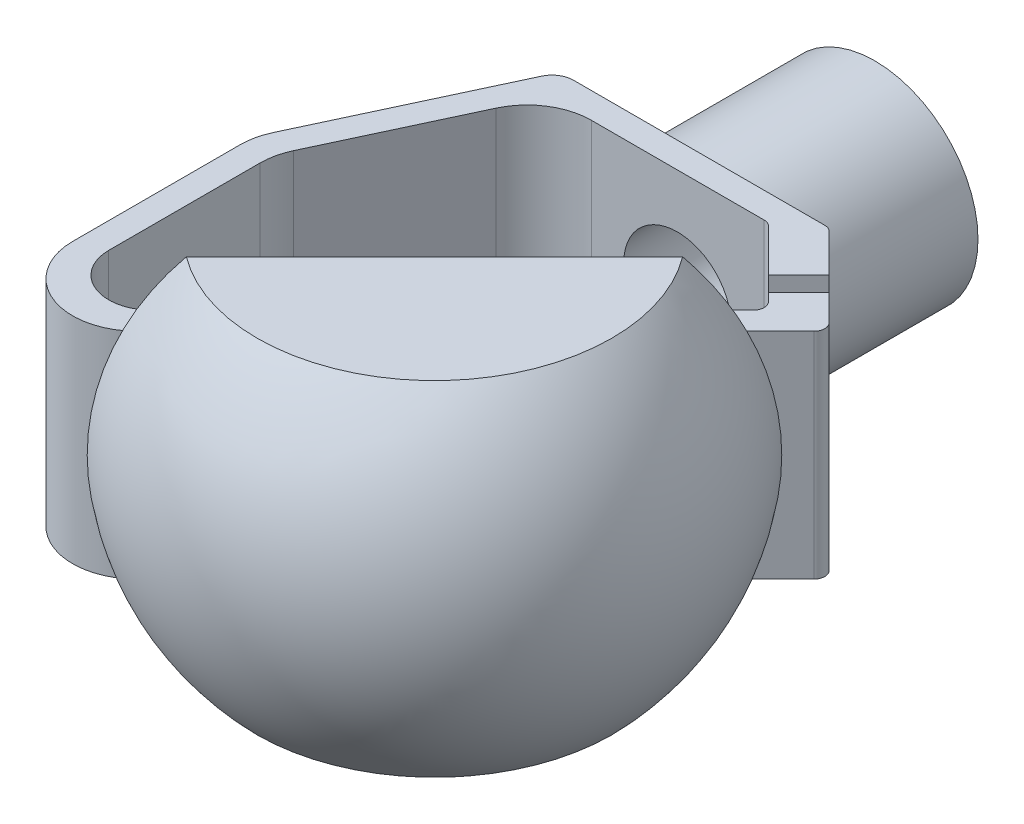
SolidWorks part; units mm, degrees
ref_plane "前视基准面" through (0, 0, 0) normal (0, 0, 1) x (1, 0, 0)
ref_plane "上视基准面" through (0, 0, 0) normal (0, 1, 0) x (1, 0, 0)
ref_plane "右视基准面" through (0, 0, 0) normal (1, 0, 0) x (0, 0, -1)
sketch "Sketch1" plane through (0, 0, 0) normal (0, 0, 1) x (1, 0, 0)
  circle A0 centre (0, 0) radius 3
  circle A1 centre (0, 0) radius 4.5
  dimension "D1" = 6
  dimension "D2" = 9
extrude "Boss-Extrude1" [suppressed] add sketch "Sketch1" along normal blind 5
sketch "Sketch2" [suppressed] plane through (0, 0, 0) normal (1, 0, 0) x (0, 0, -1)
  line L0 (5.3369, 0) -> (-52.9803, 0) construction
  line L1 (-5, 5) -> (-5, -5)
  line L2 (-5, 4.5) -> (-5, -4.5) construction
  line L3 (-6.5, 5) -> (-6.5, -1.5693)
  line L7 (-6.5, 3.4118) -> (-6.5, -3.739) construction
  line L8 (-5, 5) -> (-6.5, 5)
  arc A0 (-8.6581, -6.1507) -> (-8.6581, 6.1507) centre (-12, 0) cw
  arc A2 (-8.6581, -6.1507) -> (-5, -5) centre (-3.8839, -14.9375) cw
  arc A3 (-9.3742, -4.8327) -> (-9.5885, 4.9431) centre (-12, 0) cw
  arc A5 (-9.3742, -4.8327) -> (-8.3381, -4.3351) centre (-3.8839, -14.9375) cw
  arc A6 (-8.6581, 6.1507) -> (-5, 5) centre (-5.9228, 8.4562) ccw construction
  arc A7 (-9.5885, 4.9431) -> (-6.5, 3.4118) centre (-5.9228, 8.4562) ccw construction
  arc A8 (-8.6581, 6.1507) -> (-6.96, 4.8578) centre (-12, 0) cw
  arc A9 (-9.5885, 4.9431) -> (-8.04, 3.8169) centre (-12, 0) cw
  arc A10 (-6.96, 4.8578) -> (-8.04, 3.8169) centre (-7.5, 4.3373) cw
  arc A11 (-9.3742, -4.8327) -> (-6.5, -3.739) centre (-3.8839, -14.9375) cw construction
  arc A12 (-6.5, -1.5693) -> (-8.3381, -4.3351) centre (-9.5, -1.5693) cw
  point P14 (-5, 0)
  dimension "D1" = 7
  dimension "D2" = 7
  dimension "D3" = 10
  dimension "D6" = 3
  dimension "D5" = 10
  dimension "D7" = 2.5
  dimension "D4" = 1.5
extrude "Boss-Extrude2" [suppressed] add sketch "Sketch2" along normal mid plane 5
sketch "Sketch4" [suppressed] plane through (0, 0, 5) normal (0, 0, -1) x (-1, 0, 0)
  line L2 (-2.5, 1.6583) -> (-2.5, -1.6583)
  line L3 (-2.5, 1.6583) -> (-2.5, -1.6583)
  line L4 (2.5, -1.6583) -> (2.5, 1.6583)
  line L5 (2.5, -1.6583) -> (2.5, 1.6583)
  arc A1 (2.5, 1.6583) -> (-2.5, 1.6583) centre (0, 0) ccw
  arc A4 (2.5, 1.6583) -> (-2.5, 1.6583) centre (0, 0) ccw
  arc A5 (-2.5, -1.6583) -> (2.5, -1.6583) centre (0, 0) ccw
  arc A6 (-2.5, -1.6583) -> (2.5, -1.6583) centre (0, 0) ccw
  dimension "D1" = 0
extrude "Cut-Extrude1" [suppressed] cut sketch "Sketch4" against normal blind 10
sketch "Sketch5" [suppressed] plane through (0, 0, 0) normal (0, 1, 0) x (1, 0, 0)
  line L0 (0, 5.4882) -> (0, -28.2063) construction
  line L1 (-3, -6.75) -> (-2.5, -5.2112)
  line L2 (2.5, -6.75) -> (-2.5, -6.75) construction
  line L3 (-2.5, -6.96) -> (-2.5, -19) construction
  line L4 (-2.5, -5.2112) -> (-7.6027, -5.2112)
  line L5 (-7.6027, -5.2112) -> (-7.6027, -6.75)
  line L6 (-7.6027, -6.75) -> (-3, -6.75)
  line L7 (7.6027, -6.75) -> (3, -6.75)
  line L8 (7.6027, -5.2112) -> (7.6027, -6.75)
  line L9 (2.5, -5.2112) -> (7.6027, -5.2112)
  line L10 (3, -6.75) -> (2.5, -5.2112)
  dimension "D1" = 6
  dimension "D2" = 72
extrude "Cut-Extrude2" [suppressed] cut sketch "Sketch5" along normal blind 10
sketch "Sketch6" [suppressed] plane through (0, 0, 5) normal (0, 0, -1) x (-1, 0, 0)
  line L0 (2.5, 5) -> (0, 5) construction
  line L1 (2.5, 4.3301) -> (2.5, 5) construction
  line L2 (-2.5, 5) -> (-2.5, 4.3301) construction
  line L3 (0, 5) -> (-2.5, 5) construction
  line L4 (2.5, 5) -> (0, 5)
  line L5 (2.5, 4.3301) -> (2.5, 5)
  line L6 (-2.5, 5) -> (-2.5, 4.3301)
  line L7 (0, 5) -> (-2.5, 5)
  arc A0 (2.5, 4.3301) -> (0, 5) centre (0, 0) ccw construction
  arc A1 (0, 5) -> (-2.5, 4.3301) centre (0, 0) ccw construction
  arc A2 (2.5, 4.3301) -> (0, 5) centre (0, 0) ccw
  arc A3 (0, 5) -> (-2.5, 4.3301) centre (0, 0) ccw
extrude "Cut-Extrude3" [suppressed] cut sketch "Sketch6" against normal blind 1.5 contours A2 L5 L4
sketch "Sketch7" [suppressed] plane through (0, 0, 0) normal (0, 1, 0) x (1, 0, 0)
  line L0 (0, 0) -> (0, -16.4879) construction
  line L1 (-0.6, -10) -> (-0.6, -15)
  line L2 (-0.6, -15) -> (-2.1, -15)
  line L3 (-2.1, -15) -> (-2.1, -13.5)
  line L4 (-2.1, -10) -> (-0.6, -10)
  line L11 (-5.15, -13) -> (-7.8791, -13)
  line L13 (-5.75, -12.4) -> (-7.1299, -12.4)
  line L15 (-5.75, -12.4) -> (-2.6, -12.4)
  line L17 (-2.1, -11.9) -> (-2.1, -10)
  line L18 (-4.5, -5) -> (-1.5, -5)
  line L20 (-3.5, -7) -> (-1.5, -7)
  line L21 (-1.5, -7) -> (-1.5, -5)
  line L23 (-4.5, -5) -> (4.5, -5) construction
  line L27 (-5.15, -13) -> (-2.6, -13)
  line L36 (5.15, -13) -> (2.6, -13)
  line L40 (1.5, -7) -> (1.5, -5)
  line L41 (3.5, -7) -> (1.5, -7)
  line L42 (4.5, -5) -> (1.5, -5)
  line L43 (2.1, -11.9) -> (2.1, -10)
  line L44 (5.75, -12.4) -> (2.6, -12.4)
  line L45 (5.75, -12.4) -> (7.1299, -12.4)
  line L46 (5.15, -13) -> (7.8791, -13)
  line L47 (2.1, -10) -> (0.6, -10)
  line L48 (2.1, -15) -> (2.1, -13.5)
  line L49 (0.6, -15) -> (2.1, -15)
  line L50 (0.6, -10) -> (0.6, -15)
  arc A0 (-4.5, -5) -> (-7.8791, -13) centre (0, -11.6144) ccw
  arc A2 (-7.3792, -12.1687) -> (-7.2113, -9.9538) centre (0, -11.6144) cw
  arc A10 (-7.1299, -12.4) -> (-7.3792, -12.1687) centre (-7.1299, -12.15) cw
  arc A17 (-2.6, -13) -> (-2.1, -13.5) centre (-2.6, -13.5) cw
  arc A18 (-2.6, -12.4) -> (-2.1, -11.9) centre (-2.6, -11.9) ccw
  arc A19 (-7.2113, -9.9538) -> (-3.5, -7) centre (-3.5, -10.8084) cw
  arc A36 (7.2113, -9.9538) -> (3.5, -7) centre (3.5, -10.8084) ccw
  arc A37 (2.6, -12.4) -> (2.1, -11.9) centre (2.6, -11.9) cw
  arc A38 (2.6, -13) -> (2.1, -13.5) centre (2.6, -13.5) ccw
  arc A39 (7.1299, -12.4) -> (7.3792, -12.1687) centre (7.1299, -12.15) ccw
  arc A40 (7.3792, -12.1687) -> (7.2113, -9.9538) centre (0, -11.6144) ccw
  arc A41 (4.5, -5) -> (7.8791, -13) centre (0, -11.6144) cw
  point P37 (-2.1, -12.4)
  dimension "D4" = 8
  dimension "D1" = 0.6
  dimension "D3" = 5
  dimension "D6" = 2.4
  dimension "D11" = 0.5
  dimension "D12" = 0.25
  dimension "1.2" = 1.2
  dimension "D2" = 1.5
  dimension "D5" = 3
  dimension "D15" = 2
  dimension "D18" = 2
  dimension "D19" = 2
  dimension "0.5" = 0.6
extrude "Boss-Extrude3" [suppressed] add sketch "Sketch7" along normal mid plane 6
sketch "Sketch9" [suppressed] plane through (0, 0, 7) normal (0, 0, 1) x (1, 0, 0)
  circle A0 centre (0, 0) radius 1.5
  circle A2 centre (0, 0) radius 4.5
  arc A3 (3.3541, 3) -> (2.5, 3.7417) centre (0, 0) ccw construction
  dimension "D1" = 3
extrude "Boss-Extrude9" [suppressed] add sketch "Sketch9" against normal blind 2
sketch "Sketch10" [suppressed] plane through (0, 0, 15) normal (0, 0, 1) x (1, 0, 0)
  circle A0 centre (0, 0) radius 0.6
  circle A1 centre (0, 0) radius 2
  dimension "D1" = 1.2
  dimension "D2" = 4
extrude "Boss-Extrude10" [suppressed] add sketch "Sketch10" against normal up to surface (5 mm away)
sketch "Sketch11" [suppressed] plane through (0, 0, 15) normal (0, 0, 1) x (1, 0, 0)
  line L0 (13.3922, 0) -> (-14.7253, 0) construction
  line L1 (0.6, 1.9079) -> (4, 1.9079)
  line L2 (4, 1.9079) -> (6.219, 3.189)
  line L3 (6.219, 3.189) -> (-6.219, 3.189)
  line L4 (0, 3.189) -> (0, 2) construction
  line L5 (-4, 1.9079) -> (-6.219, 3.189)
  line L6 (-0.6, 1.9079) -> (-4, 1.9079)
  line L7 (-0.6, -1.9079) -> (-4, -1.9079)
  line L8 (-4, -1.9079) -> (-6.219, -3.189)
  line L9 (6.219, -3.189) -> (-6.219, -3.189)
  line L10 (4, -1.9079) -> (6.219, -3.189)
  line L11 (0.6, -1.9079) -> (4, -1.9079)
  arc A0 (0.6, 1.9079) -> (-0.6, 1.9079) centre (0, 0) ccw construction
  arc A1 (0.6, 1.9079) -> (-0.6, 1.9079) centre (0, 0) ccw
  arc A2 (0.6, -1.9079) -> (-0.6, -1.9079) centre (0, 0) cw
  line M9 (-0.6, -3) -> (-0.6, -1.9079)
  arc M10 (-0.6, -1.9079) -> (0.6, -1.9079) centre (0, 0) ccw
  line M11 (0.6, -1.9079) -> (0.6, -3)
  line M12 (0.6, -3) -> (2.1, -3)
  line M13 (2.1, -3) -> (2.1, 3)
  line M14 (2.1, 3) -> (0.6, 3)
  line M15 (0.6, 3) -> (0.6, 1.9079)
  arc M16 (0.6, 1.9079) -> (-0.6, 1.9079) centre (0, 0) ccw
  line M17 (-0.6, 1.9079) -> (-0.6, 3)
  line M18 (-0.6, 3) -> (-2.1, 3)
  line M19 (-2.1, 3) -> (-2.1, -3)
  line M20 (-2.1, -3) -> (-0.6, -3)
  dimension "D1" = 30
  dimension "D2" = 4
extrude "Cut-Extrude5" [suppressed] cut sketch "Sketch11" against normal blind 5 contours L6 L1 L2 L3 L5 M19 M18 M17 M16 M15 M14 M13 | L11 L7 L8 L9 L10 M13 M12 M11 M10 M9 M20 M19
sketch "Sketch12" [suppressed] plane through (0, 0, 15) normal (0, 0, 1) x (1, 0, 0)
  line L0 (-0.6, 1.9079) -> (-2.1, 1.9079)
  line L1 (0.6, 1.9079) -> (2.1, 1.9079)
  line L2 (-2.1, -1.9079) -> (-0.6, -1.9079)
  line L3 (0.6, -1.9079) -> (2.1, -1.9079)
  line L4 (-2.1, -1.9079) -> (-2.1, -3)
  line L5 (2.1, 1.9079) -> (2.1, 3)
  line L10 (-0.6, -3) -> (-0.6, -1.9079)
  line L11 (0.6, -1.9079) -> (0.6, -3)
  line L12 (0.6, -3) -> (2.1, -3)
  line L13 (2.1, -3) -> (2.1, 3)
  line L14 (2.1, 3) -> (0.6, 3)
  line L15 (0.6, 3) -> (0.6, 1.9079)
  line L16 (-0.6, 1.9079) -> (-0.6, 3)
  line L17 (-0.6, 3) -> (-2.1, 3)
  line L18 (-2.1, 3) -> (-2.1, -3)
  line L19 (-2.1, -3) -> (-0.6, -3)
  line L20 (-0.6, -3) -> (-0.6, -1.9079)
  line L21 (0.6, -1.9079) -> (0.6, -3)
  line L22 (0.6, -3) -> (2.1, -3)
  line L23 (2.1, -3) -> (2.1, -1.9079)
  line L24 (2.1, 3) -> (0.6, 3)
  line L25 (0.6, 3) -> (0.6, 1.9079)
  line L26 (-0.6, 1.9079) -> (-0.6, 3)
  line L27 (-0.6, 3) -> (-2.1, 3)
  line L28 (-2.1, 3) -> (-2.1, 1.9079)
  line L29 (-2.1, -3) -> (-0.6, -3)
  arc A2 (-0.6, -1.9079) -> (0.6, -1.9079) centre (0, 0) ccw
  arc A3 (0.6, 1.9079) -> (-0.6, 1.9079) centre (0, 0) ccw
  dimension "D1" = 0
extrude "Cut-Extrude6" [suppressed] cut sketch "Sketch12" against normal blind 5
fillet "Fillet1" [suppressed] radius 0.5
sketch "Sketch13" [suppressed] plane through (0, 0, 13) normal (0, 0, 1) x (1, 0, 0)
  line L0 (-9.2479, 0) -> (9.577, 0) construction
  line L1 (-7.3, -0.3079) -> (-7.3, 0.3079)
  line L2 (-4.1072, 0.9079) -> (-2.7, 0.9079)
  line L3 (-2.1, 0.3079) -> (-2.1, -0.3079)
  line L5 (0, 3.8752) -> (0, -3.6778) construction
  line L7 (2.1, 0.3079) -> (2.1, -0.3079)
  line L9 (7.3, -0.3079) -> (7.3, 0.3079)
  line L11 (-4, 1.9079) -> (-2.6, 1.9079) construction
  line L12 (-2.1, 1.9079) -> (-2.1, -1.9079) construction
  line L13 (-7.3, 0.3079) -> (-7.3, 1.4)
  line L14 (-6.7, 2) -> (-6.3203, 2)
  line L15 (-6.0203, 1.9196) -> (-4.4072, 0.9883)
  line L16 (-6.0203, -1.9196) -> (-4.4072, -0.9883)
  line L17 (-6.7, -2) -> (-6.3203, -2)
  line L18 (-7.3, -0.3079) -> (-7.3, -1.4)
  line L19 (6.0203, -1.9196) -> (4.4072, -0.9883)
  line L20 (6.7, -2) -> (6.3203, -2)
  line L21 (7.3, -0.3079) -> (7.3, -1.4)
  line L22 (7.3, 0.3079) -> (7.3, 1.4)
  line L23 (6.7, 2) -> (6.3203, 2)
  line L24 (6.0203, 1.9196) -> (4.4072, 0.9883)
  line L25 (-4.1072, -0.9079) -> (-2.7, -0.9079)
  line L26 (2.7, 0.9079) -> (4.1072, 0.9079)
  line L27 (2.7, -0.9079) -> (4.1072, -0.9079)
  line L28 (-5.8916, 3) -> (-4, 1.9079) construction
  line L29 (-7.4475, -3) -> (-5.8916, -3) construction
  arc A2 (2.1, 0.3079) -> (2.7, 0.9079) centre (2.7, 0.3079) cw
  arc A3 (2.7, -0.9079) -> (2.1, -0.3079) centre (2.7, -0.3079) cw
  arc A5 (-2.7, -0.9079) -> (-2.1, -0.3079) centre (-2.7, -0.3079) ccw
  arc A6 (-2.7, 0.9079) -> (-2.1, 0.3079) centre (-2.7, 0.3079) cw
  arc A8 (4.4072, -0.9883) -> (4.1072, -0.9079) centre (4.1072, -1.5079) ccw
  arc A9 (6.0203, -1.9196) -> (6.3203, -2) centre (6.3203, -1.4) ccw
  arc A10 (6.7, -2) -> (7.3, -1.4) centre (6.7, -1.4) ccw
  arc A11 (7.3, 1.4) -> (6.7, 2) centre (6.7, 1.4) ccw
  arc A12 (6.3203, 2) -> (6.0203, 1.9196) centre (6.3203, 1.4) ccw
  arc A13 (4.4072, 0.9883) -> (4.1072, 0.9079) centre (4.1072, 1.5079) cw
  arc A14 (-4.4072, 0.9883) -> (-4.1072, 0.9079) centre (-4.1072, 1.5079) ccw
  arc A15 (-4.4072, -0.9883) -> (-4.1072, -0.9079) centre (-4.1072, -1.5079) cw
  arc A16 (-6.0203, -1.9196) -> (-6.3203, -2) centre (-6.3203, -1.4) cw
  arc A17 (-6.7, -2) -> (-7.3, -1.4) centre (-6.7, -1.4) cw
  arc A18 (-6.3203, 2) -> (-6.0203, 1.9196) centre (-6.3203, 1.4) cw
  arc A19 (-7.3, 1.4) -> (-6.7, 2) centre (-6.7, 1.4) cw
  point P8 (-2.1, 0)
  point P9 (-7.3, 0)
  point P11 (7.3, 0)
  point P12 (2.1, 0)
  point P23 (7.3, -0.9079)
  point P26 (7.3, 0.9079)
  point P29 (2.1, 0.9079)
  point P32 (2.1, -0.9079)
  point P35 (-7.3, -0.9079)
  point P38 (-2.1, -0.9079)
  point P41 (-2.1, 0.9079)
  point P44 (-7.3, 0.9079)
  point P55 (4.2679, -0.9079)
  point P58 (6.1596, -2)
  point P61 (7.3, -2)
  point P64 (7.3, 2)
  point P67 (6.1596, 2)
  point P70 (4.2679, 0.9079)
  point P73 (-4.2679, 0.9079)
  point P76 (-4.2679, -0.9079)
  point P79 (-6.1596, -2)
  point P82 (-7.3, -2)
  point P85 (-6.1596, 2)
  point P88 (-7.3, 2)
  dimension "D4" = 1
  dimension "D5" = 0.6
  dimension "D6" = 0.6
  dimension "D1" = 1
  dimension "D2" = 5.2
  dimension "D3" = 1
extrude "Cut-Extrude7" [suppressed] cut sketch "Sketch13" against normal blind 1 and the other way blind 1
sketch "Sketch14" [suppressed] plane through (0, 0, 15) normal (0, 0, 1) x (1, 0, 0)
  line L6 (-0.6, 1.9079) -> (-2.1, 1.9079)
  line L7 (-2.1, 1.9079) -> (-2.1, -1.9079)
  line L8 (-2.1, -1.9079) -> (-0.6, -1.9079)
  line L9 (0.6, -1.9079) -> (2.1, -1.9079)
  line L10 (2.1, -1.9079) -> (2.1, 1.9079)
  line L11 (2.1, 1.9079) -> (0.6, 1.9079)
  line L12 (-0.6, 1.9079) -> (-2.1, 1.9079)
  line L13 (-2.1, 1.9079) -> (-2.1, -1.9079)
  line L14 (-2.1, -1.9079) -> (-0.6, -1.9079)
  line L15 (0.6, -1.9079) -> (2.1, -1.9079)
  line L16 (2.1, -1.9079) -> (2.1, 1.9079)
  line L17 (2.1, 1.9079) -> (0.6, 1.9079)
  circle A0 centre (0, 0) radius 1.75
  arc A2 (0.6, 1.9079) -> (-0.6, 1.9079) centre (0, 0) ccw
  arc A3 (-0.6, -1.9079) -> (0.6, -1.9079) centre (0, 0) ccw
  arc A4 (0.6, 1.9079) -> (-0.6, 1.9079) centre (0, 0) ccw
  arc A5 (-0.6, -1.9079) -> (0.6, -1.9079) centre (0, 0) ccw
  dimension "D2" = 3.5
  dimension "D1" = 0
extrude "Cut-Extrude8" [suppressed] cut sketch "Sketch14" against normal blind 1.5
sketch "Sketch15" [suppressed] plane through (0, 0, 10) normal (0, 0, -1) x (-1, 0, 0)
  line L6 (2.1, -1.9079) -> (2.1, 1.9079)
  line L7 (2.1, 1.9079) -> (0.6, 1.9079)
  line L8 (-0.6, 1.9079) -> (-2.1, 1.9079)
  line L9 (-2.1, 1.9079) -> (-2.1, -1.9079)
  line L10 (-2.1, -1.9079) -> (-0.6, -1.9079)
  line L11 (0.6, -1.9079) -> (2.1, -1.9079)
  line L12 (2.1, -1.9079) -> (2.1, 1.9079)
  line L13 (2.1, 1.9079) -> (0.6, 1.9079)
  line L14 (-0.6, 1.9079) -> (-2.1, 1.9079)
  line L15 (-2.1, 1.9079) -> (-2.1, -1.9079)
  line L16 (-2.1, -1.9079) -> (-0.6, -1.9079)
  line L17 (0.6, -1.9079) -> (2.1, -1.9079)
  circle A0 centre (0, 0) radius 1.75
  arc A2 (0.6, 1.9079) -> (-0.6, 1.9079) centre (0, 0) ccw
  arc A3 (-0.6, -1.9079) -> (0.6, -1.9079) centre (0, 0) ccw
  arc A4 (0.6, 1.9079) -> (-0.6, 1.9079) centre (0, 0) ccw
  arc A5 (-0.6, -1.9079) -> (0.6, -1.9079) centre (0, 0) ccw
  dimension "D2" = 3.5
  dimension "D1" = 0
extrude "Cut-Extrude11" [suppressed] cut sketch "Sketch15" against normal blind 1.9
fillet "Fillet2" [suppressed] radius 0.5
fillet "Fillet3" [suppressed] radius 0.5
sketch "Sketch16" plane through (0, 0, 0) normal (0, 1, 0) x (1, 0, 0)
  line L0 (0, 4.0945) -> (0, -2.9745) construction
  line L1 (0, 0) -> (-2.4, 0)
  line L2 (-2.4, 0) -> (-2.4, -4)
  line L3 (-2.4, -4) -> (0, -4)
  line L4 (0, 0) -> (0, -4)
  dimension "D1" = 4
  dimension "D2" = 4.8
revolve "Revolve1" add sketch "Sketch16" angle 360 about L0
sketch "Sketch18" plane through (0, 0, 0) normal (0, 1, 0) x (1, 0, 0)
  line L0 (0, -4) -> (-3.0193, -4)
  line L1 (-3.4725, -4.2887) -> (-5.4595, -8.5498)
  line L2 (-5.6, -9.1837) -> (-5.6, -13.0841)
  line L3 (-3.0393, -14.1447) -> (4.8437, -6.2617)
  line L5 (2.832, -4) -> (0, -4)
  line L6 (-2.4, -4) -> (2.4, -4) construction
  line L7 (0, -4) -> (0, -5.5861) construction
  line L8 (0, -4.6) -> (-2, -4.6)
  line L9 (-3.3595, -5.4661) -> (-4.8595, -8.6828)
  line L10 (-5, -9.3168) -> (-5, -12.8426)
  line L11 (-3.2929, -13.5497) -> (3.7123, -6.5445)
  line L13 (2.0178, -4.6) -> (0, -4.6)
  line L14 (-5, -8.9842) -> (-5, -15.2569) construction
  line L15 (-5, -15.2569) -> (3.6328, -6.624) construction
  line L16 (-5.6, -8.8512) -> (-5.6, -16.7054) construction
  line L17 (-5.6, -16.7054) -> (4.2328, -6.8725) construction
  line L18 (0, -4.6) -> (-2.9556, -4.6) construction
  line L19 (-2.9556, -4.6) -> (-5, -8.9842) construction
  line L20 (-3.3378, -4) -> (-5.6, -8.8512) construction
  line L27 (4.2328, -4) -> (0, -4) construction
  line L28 (3.6328, -4.6) -> (0, -4.6) construction
  line L29 (0, -4) -> (-3.3378, -4) construction
  line L30 (2.1945, -4.6732) -> (3.182, -5.6607)
  line L31 (3.182, -5.6607) -> (3.8891, -4.9536)
  line L32 (3.8891, -4.9536) -> (3.0088, -4.0732)
  line L33 (3.6328, -6.624) -> (3.6328, -4.6) construction
  line L34 (4.2328, -6.8725) -> (4.2328, -4) construction
  line L35 (3.7123, -6.191) -> (3.5355, -6.0142)
  line L36 (3.5355, -6.0142) -> (4.2426, -5.3071)
  line L37 (4.2426, -5.3071) -> (4.8437, -5.9081)
  arc A0 (-5, -12.8426) -> (-3.2929, -13.5497) centre (-4, -12.8426) ccw
  arc A1 (-5.6, -13.0841) -> (-3.0393, -14.1447) centre (-4.1, -13.0841) ccw
  arc A2 (-2, -4.6) -> (-3.3595, -5.4661) centre (-2, -6.1) ccw
  arc A3 (-4.8595, -8.6828) -> (-5, -9.3168) centre (-3.5, -9.3168) ccw
  arc A4 (-5.4595, -8.5498) -> (-5.6, -9.1837) centre (-4.1, -9.1837) ccw
  arc A9 (-3.0193, -4) -> (-3.4725, -4.2887) centre (-3.0193, -4.5) ccw
  arc A10 (2.832, -4) -> (3.0088, -4.0732) centre (2.832, -4.25) cw
  arc A11 (2.0178, -4.6) -> (2.1945, -4.6732) centre (2.0178, -4.85) cw
  arc A12 (4.8437, -6.2617) -> (4.8437, -5.9081) centre (4.6669, -6.0849) ccw
  arc A13 (3.7123, -6.5445) -> (3.7123, -6.191) centre (3.5355, -6.3678) ccw
  point P51 (3.8891, -6.3678)
  dimension "D5" = 1
  dimension "D6" = 1.5
  dimension "D7" = 1.5
  dimension "D9" = 4
  dimension "D15" = 0.25
  dimension "D16" = 0.5
  dimension "D2" = 1
  dimension "D3" = 65
  dimension "D4" = 45
  dimension "D8" = 0.5
  dimension "D10" = 0.5
  dimension "D11" = 2.5
  dimension "D12" = 5
  dimension "D13" = 0.6
  dimension "D14" = 0.6
  dimension "D17" = 2
extrude "Boss-Extrude11" add sketch "Sketch18" along normal mid plane 5
sketch "Sketch19" plane through (0, 0, 0) normal (0, 0, -1) x (-1, 0, 0)
  circle A0 centre (0, 0) radius 1.25
  dimension "D1" = 2.5
extrude "Cut-Extrude12" cut sketch "Sketch19" against normal blind 5
sketch "Sketch20" plane through (0, 0, 0) normal (0, 1, 0) x (1, 0, 0)
  line L0 (4.4548, -6.6506) -> (-3.677, -14.7823)
  line L1 (-3.0393, -14.1447) -> (4.8437, -6.2617) construction
  line L2 (-3.677, -14.7823) -> (-0.1414, -18.3179)
  line L3 (-0.1414, -18.3179) -> (7.9903, -10.1861)
  line L4 (7.9903, -10.1861) -> (4.4548, -6.6506)
  line L5 (3.5355, -6.0142) -> (3.7123, -6.191) construction
  dimension "D1" = 11.5
  dimension "D2" = 5
  dimension "D3" = 0.2
extrude "Boss-Extrude12" [suppressed] add sketch "Sketch20" along normal mid plane 10 separate body
sketch "Sketch21" [suppressed] plane through (0, 0, 0) normal (0, 1, 0) x (1, 0, 0)
  line L0 (0, 0) -> (0, -10.2569) construction
  line L1 (3.7123, -6.5445) -> (-3.2929, -13.5497) construction
  line L2 (4.4548, -6.6506) -> (4.9281, -9.4121) construction
  line L3 (0.3889, -10.7165) -> (3.5, -13.8276) construction
  line L4 (4.4548, -6.6506) -> (-3.677, -14.7823) construction
  line L5 (3.5, -13.8276) -> (5.8896, -11.4853) construction
  circle A0 centre (0, -10.2569) radius 5 construction
  dimension "D1" = 10
sketch "Sketch22" plane through (0, 0, 0) normal (0, -1, 0) x (1, 0, 0)
  line L0 (0, 0) -> (0, 10.2569) construction
  line L2 (3.7123, 6.5445) -> (-3.2929, 13.5497) construction
  line L3 (0, 10.2569) -> (5.1687, 15.4255) construction
  line L5 (-3.0393, 14.1447) -> (4.8437, 6.2617) construction
  line L6 (0.4243, 10.6811) -> (-3.6194, 14.7248)
  line L7 (0.4243, 10.6811) -> (4.0659, 14.3227)
  circle A0 centre (0, 10.2569) radius 5.75 construction
  arc A1 (-3.6194, 14.7248) -> (4.0659, 14.3227) centre (0, 10.2569) cw
  dimension "D1" = 11.5
revolve "Revolve2" add sketch "Sketch22" angle 360 about L3
sketch "Sketch23" plane through (5.5527, 0, 5.5527) normal (-0.7071, 0, -0.7071) x (-0.7071, 0, 0.7071)
  line L0 (0, 0) -> (17.49, 0) construction
  line L1 (11.3396, 4) -> (3.1658, 4)
  line L2 (11.3396, -4) -> (3.1658, -4)
  arc A0 (2.1095, -2.5) -> (2.1095, 2.5) centre (7.2527, 0) ccw construction
  arc A1 (3.1658, -4) -> (11.3396, -4) centre (7.2527, 0) ccw
  arc A2 (11.3396, 4) -> (3.1658, 4) centre (7.2527, 0) ccw
  dimension "D1" = 4
  dimension "D2" = 4
extrude "Cut-Extrude13" cut sketch "Sketch23" against normal blind 10
